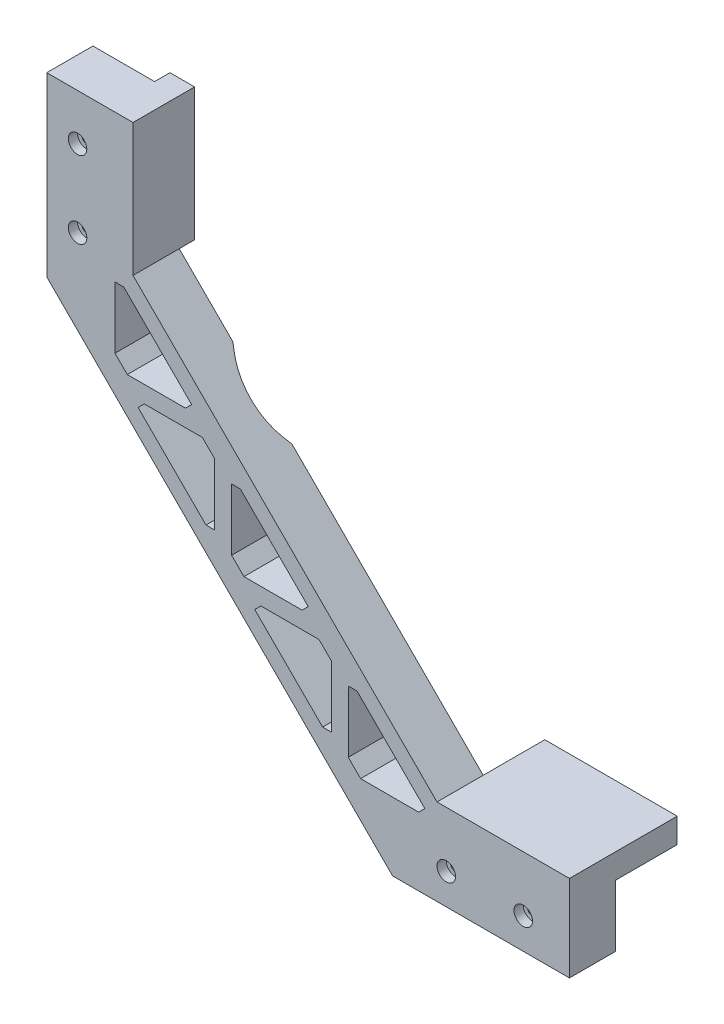
SolidWorks part; units mm, degrees
ref_plane "前视基准面" through (0, 0, 0) normal (0, 0, 1) x (1, 0, 0)
ref_plane "上视基准面" through (0, 0, 0) normal (0, 1, 0) x (1, 0, 0)
ref_plane "右视基准面" through (0, 0, 0) normal (1, 0, 0) x (0, 0, -1)
other "Configuration Table"
sketch "草图1" plane through (0, 0, 0) normal (0, 0, 1) x (1, 0, 0)
  line L0 (124.695, -160) -> (159.695, -160)
  line L1 (172.695, -180) -> (-7.695, -180) construction
  line L2 (159.695, -160) -> (159.695, -180)
  line L3 (159.695, -180) -> (102.2686, -180)
  line L4 (102.2686, -180) -> (-10, -67.7314)
  line L5 (17.8609, -53.1659) -> (-3.3523, -74.3791) construction
  line L6 (-10, -67.7314) -> (-10, -10.305)
  line L7 (-10, -10.305) -> (10, -10.305)
  line L8 (10, -10.305) -> (10, -45.305)
  line L9 (10, -45.305) -> (124.695, -160)
  line L10 (-10, 104.4) -> (-10, -160) construction
  line L11 (10, 104.4) -> (10, -160) construction
  line L12 (-14.695, -160) -> (159.695, -160) construction
  line L14 (159.695, -172.7737) -> (159.695, -167.2263) construction
  dimension "D1" = 35
  dimension "D2" = 35
  dimension "D3" = 30
extrude "凸台-拉伸1" add sketch "草图1" along normal blind 15
sketch "草图3" plane through (0, 0, 15) normal (0, 0, 1) x (1, 0, 0)
  line L0 (159.695, -160) -> (116.695, -160)
  line L2 (124.695, -160) -> (10, -45.305) construction
  line L3 (116.695, -152) -> (159.695, -152)
  line L4 (159.695, -152) -> (159.695, -160)
  line L5 (116.695, -152) -> (116.695, -160)
  point P4 (0, 0)
  point P10 (116.4673, -160)
  dimension "D1" = 8
extrude "凸台-拉伸2" add sketch "草图3" against normal blind 35
sketch "草图4" plane through (0, 0, 15) normal (0, 0, 1) x (1, 0, 0)
  line L0 (10, -45.305) -> (10, -10.305) construction
  line L1 (10, -10.305) -> (18, -10.305)
  line L2 (10, -10.305) -> (10, -53.305)
  line L3 (10, -53.305) -> (18, -53.305)
  line L4 (18, -10.305) -> (18, -53.305)
  line L6 (10, -10.305) -> (-10, -10.305) construction
  line L7 (116.695, -152) -> (10, -45.305) construction
  point P6 (18, -53.305)
  dimension "D1" = 8
extrude "凸台-拉伸3" add sketch "草图4" against normal blind 35
sketch "草图5" plane through (0, 0, 15) normal (0, 0, 1) x (1, 0, 0)
  line L4 (50.0234, -93.1066) -> (50.0234, -119.9766)
  line L5 (50.0234, -119.9766) -> (76.8934, -119.9766)
  line L6 (76.8934, -119.9766) -> (50.0234, -93.1066)
  line L7 (55.5234, -125.4766) -> (82.3934, -125.4766)
  line L8 (82.3934, -125.4766) -> (82.3934, -152.3467)
  line L9 (82.3934, -152.3467) -> (55.5234, -125.4766)
  line L10 (12.1533, -55.2365) -> (12.1533, -82.1066)
  line L11 (12.1533, -82.1066) -> (39.0234, -82.1066)
  line L12 (39.0234, -82.1066) -> (12.1533, -55.2365)
  line L13 (87.8934, -130.9766) -> (87.8934, -157.8467)
  line L15 (116.695, -152) -> (18, -53.305) construction
  line L16 (17.6533, -87.6066) -> (44.5234, -87.6066)
  line L17 (44.5234, -87.6066) -> (44.5234, -114.4766)
  line L18 (44.5234, -114.4766) -> (17.6533, -87.6066)
  line L19 (-10, -67.7314) -> (102.2686, -180) construction
  line L20 (35.9264, -79.0096) -> (39.7761, -82.8593) construction
  line L21 (15.6753, -85.6286) -> (-21.6148, -48.3384) construction
  line L22 (33.1355, -76.2186) -> (37.0245, -72.3295) construction
  line L23 (19.2968, -89.2501) -> (15.4078, -93.1392) construction
  line L24 (24.3585, -82.1066) -> (24.3585, -87.6066) construction
  line L25 (87.8934, -157.8467) -> (114.7635, -157.8467)
  line L26 (114.7635, -157.8467) -> (87.8934, -130.9766)
  line L27 (44.5234, -103.4947) -> (50.0234, -103.4947) construction
  line L28 (68.5928, -119.9766) -> (68.5928, -125.4766) construction
  line L29 (82.3934, -131.3401) -> (87.8934, -131.3401) construction
  line L30 (12.1533, -76.2143) -> (12.1533, -105.29) construction
  line L31 (10, -98.1526) -> (12.1533, -98.1526) construction
  line L32 (10, 104.4) -> (10, -160) construction
  line L33 (87.8934, -157.8467) -> (71.7553, -157.8467) construction
  line L35 (74.4155, -157.8467) -> (74.4155, -160) construction
  line L36 (-14.695, -160) -> (159.695, -160) construction
  point P41 (74.4368, -160)
  point P47 (74.4155, -160)
  dimension "D1" = 5.5
extrude "切除-拉伸1" cut sketch "草图5" against normal through all
sketch "草图6" plane through (0, 0, 15) normal (0, 0, 1) x (1, 0, 0)
  line L0 (2.7737, 104.4) -> (-2.7737, 104.4) construction
  line L1 (173.595, -172.7737) -> (173.595, -167.2263) construction
  line L2 (159.695, -180) -> (159.695, -152) construction
  line L3 (18, -10.305) -> (-10, -10.305) construction
  circle A0 centre (0, -50.305) radius 1.6
  circle A1 centre (0, -25.305) radius 1.6
  circle A2 centre (119.695, -170) radius 1.6
  circle A3 centre (144.695, -170) radius 1.6
  point P10 (0, 104.4)
  point P13 (173.595, -170)
  dimension "D1" = 3.2
  dimension "D2" = 15
  dimension "D3" = 25
  dimension "D4" = 15
  dimension "D5" = 25
extrude "切除-拉伸2" cut sketch "草图6" against normal through all
sketch "草图7" plane through (0, 0, 15) normal (0, 0, 1) x (1, 0, 0)
  circle A0 centre (0, -25.305) radius 3
  circle A1 centre (144.695, -170) radius 1.6
  circle A2 centre (144.695, -170) radius 1.6 construction
  circle A3 centre (119.695, -170) radius 1.6
  circle A4 centre (119.695, -170) radius 1.6 construction
  circle A5 centre (0, -25.305) radius 1.6
  circle A6 centre (0, -25.305) radius 1.6 construction
  circle A7 centre (0, -50.305) radius 1.6
  circle A8 centre (0, -50.305) radius 1.6 construction
  circle A9 centre (0, -50.305) radius 3
  circle A10 centre (119.695, -170) radius 3
  circle A11 centre (144.695, -170) radius 3
  dimension "D5" = 6
  dimension "D1" = 0
  dimension "D2" = 0
  dimension "D3" = 0
  dimension "D4" = 0
extrude "切除-拉伸3" cut sketch "草图7" against normal blind 3
chamfer "倒角1" distance 4 angle 45 15 edges at (55.5234, -125.4766, 7.5) (82.3934, -125.4766, 7.5) (87.8934, -130.9766, 7.5) (76.8934, -119.9766, 7.5) (50.0234, -119.9766, 7.5) (87.8934, -157.8467, 7.5) (114.7635, -157.8467, 7.5) (82.3934, -152.3467, 7.5) (44.5234, -114.4766, 7.5) (17.6533, -87.6066, 7.5) (44.5234, -87.6066, 7.5) (39.0234, -82.1066, 7.5) (12.1533, -82.1066, 7.5) (12.1533, -55.2365, 7.5) (50.0234, -93.1066, 7.5)
sketch "草图9" plane through (0, -10.305, 0) normal (0, 1, 0) x (1, 0, 0)
  line L5 (35.4134, 0) -> (54.5866, 0)
  line L10 (12.5, 16.2061) -> (37.0891, -1.1851)
  line L11 (52.9109, -1.1851) -> (77.5, 16.2061)
  line L12 (77.5, 16.2061) -> (77.5, 25)
  line L13 (77.5, 25) -> (12.5, 25)
  line L14 (12.5, 25) -> (12.5, 16.2061)
  line L15 (12.5, 16.2061) -> (37.0891, -1.1851)
  line L16 (52.9109, -1.1851) -> (77.5, 16.2061)
  line L17 (77.5, 16.2061) -> (77.5, 25)
  line L18 (77.5, 25) -> (12.5, 25)
  line L19 (12.5, 25) -> (12.5, 16.2061)
  arc A2 (37.0891, -1.1851) -> (52.9109, -1.1851) centre (45, 10) ccw
  arc A3 (37.0891, -1.1851) -> (52.9109, -1.1851) centre (45, 10) ccw
  dimension "D1" = 2.5
extrude "切除-拉伸4" cut sketch "草图9" against normal blind 133 contours L15 A3 L16 L5
sketch "草图10" plane through (0, -10.305, 0) normal (0, 1, 0) x (1, 0, 0)
  line L0 (10, 20) -> (10, 0) construction
  line L1 (10, 5) -> (18, 5)
  line L2 (10, 5) -> (10, 20)
  line L3 (10, 20) -> (18, 20)
  line L4 (18, 5) -> (18, 20)
  line L5 (18, 20) -> (18, -15) construction
  line L6 (18, 20) -> (10, 20) construction
  point P6 (18, 10.8384)
  dimension "D1" = 15
extrude "切除-拉伸5" cut sketch "草图10" against normal up to surface (43 mm away) up to face at (14, -53.305, -10)
